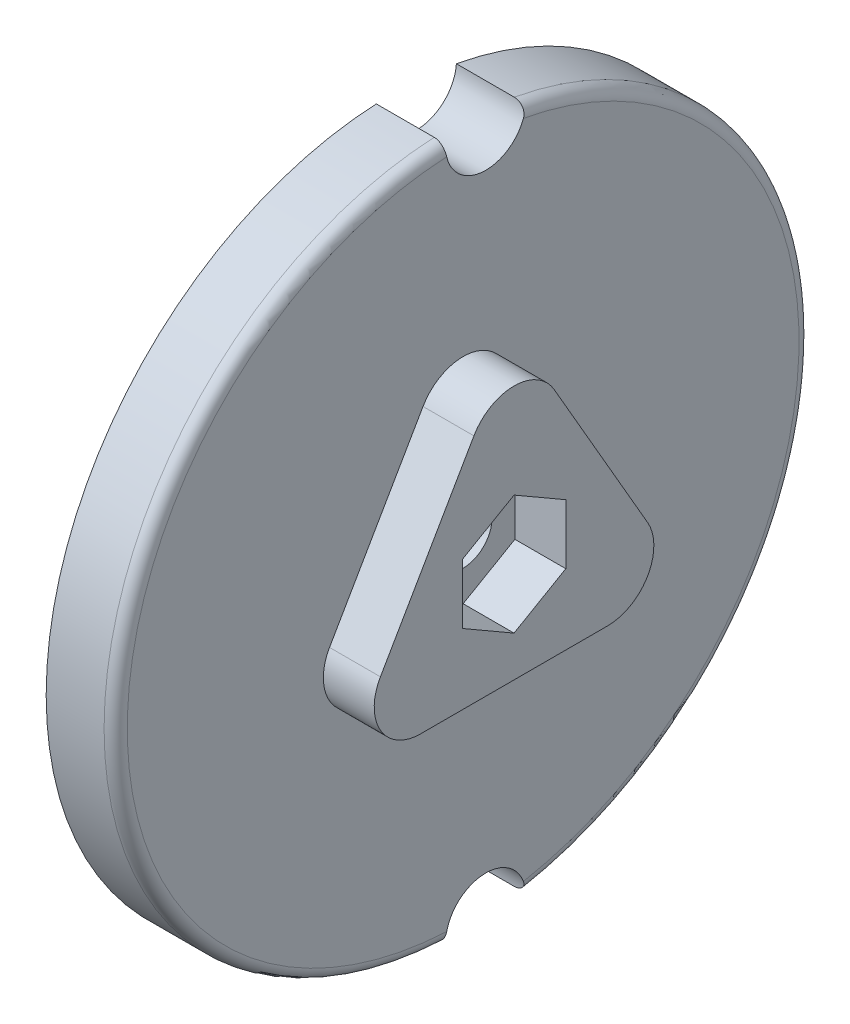
SolidWorks part; units mm, degrees
ref_plane "Front Plane" through (0, 0, 0) normal (0, 0, 1) x (1, 0, 0)
ref_plane "Top Plane" through (0, 0, 0) normal (0, 1, 0) x (1, 0, 0)
ref_plane "Right Plane" through (0, 0, 0) normal (1, 0, 0) x (0, 0, -1)
sketch "Sketch2" plane through (0, 0, 0) normal (1, 0, 0) x (0, 0, -1)
  line L0 (55, 0) -> (-55, 0) construction
  arc A0 (6.8776, -37.4741) -> (6.8776, 37.4741) centre (0, 0) ccw
  circle A1 centre (0, 0) radius 3.175
  arc A2 (-1.9043, -38.0524) -> (6.8776, -37.4741) centre (2.4867, -37.7632) cw
  arc A3 (-1.9043, 38.0524) -> (6.8776, 37.4741) centre (2.4867, 37.7632) ccw
  arc A4 (-1.9043, 38.0524) -> (-1.9043, -38.0524) centre (0, 0) ccw
  dimension "D1" = 76.2
  dimension "D2" = 6.35
extrude "Boss-Extrude1" add sketch "Sketch2" along normal blind 7.62
sketch "Sketch3" plane through (7.62, 0, 0) normal (1, 0, 0) x (0, 0, -1)
  line L0 (-5.675, 3.2765) -> (-5.675, -3.2765)
  line L1 (19.05, -10.9985) -> (0, 21.997)
  line L2 (0, 21.997) -> (-19.05, -10.9985)
  line L3 (-19.05, -10.9985) -> (19.05, -10.9985)
  line L4 (5.675, -3.2765) -> (5.675, 3.2765)
  line L5 (5.675, 3.2765) -> (0, 6.5529)
  line L6 (0, 6.5529) -> (-5.675, 3.2765)
  line L7 (-5.675, -3.2765) -> (0, -6.5529)
  line L8 (0, -6.5529) -> (5.675, -3.2765)
  circle A0 centre (0, 0) radius 10.9985 construction
  circle A1 centre (0, 0) radius 5.675 construction
  dimension "D1" = 11.35
  dimension "D2" = 38.1
extrude "Boss-Extrude2" add sketch "Sketch3" along normal blind 5.58
fillet "Fillet1" radius 5.08 3 edges at (10.41, -10.9985, -19.05) (10.41, 21.997, 0) (10.41, -10.9985, 19.05)
fillet "Fillet3" radius 1.27 2 edges at (7.62, 0, -38.1) (7.62, 0, 38.1)
